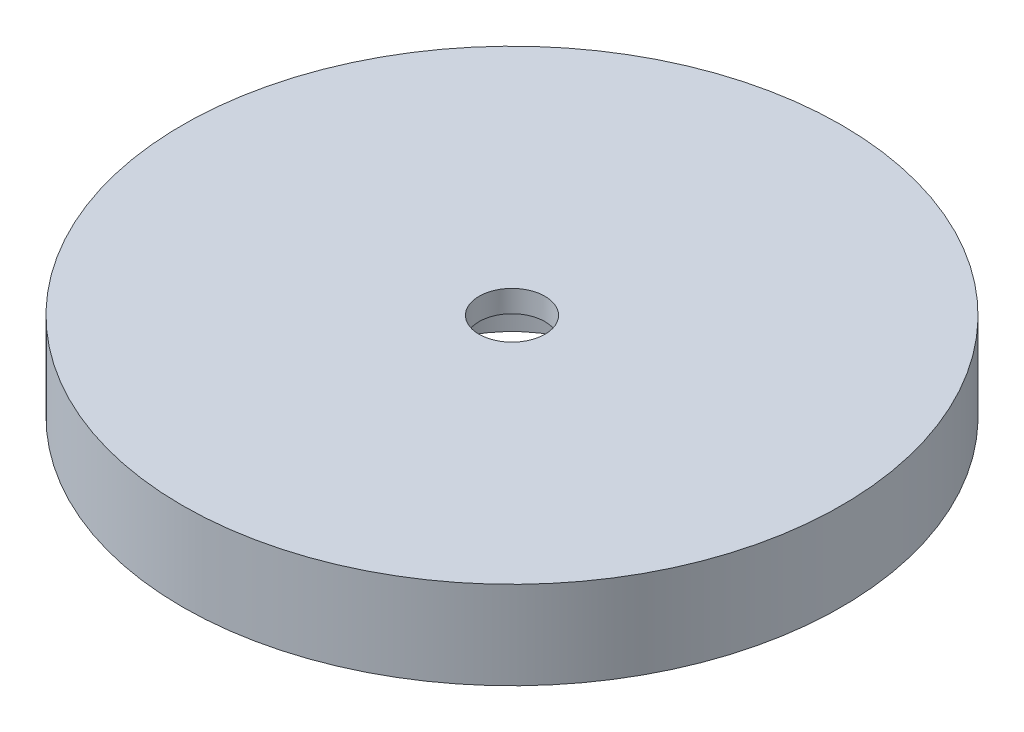
SolidWorks part; units mm, degrees
ref_plane "Plan de face" through (0, 0, 0) normal (0, 0, 1) x (1, 0, 0)
ref_plane "Plan de dessus" through (0, 0, 0) normal (0, 1, 0) x (1, 0, 0)
ref_plane "Plan de droite" through (0, 0, 0) normal (1, 0, 0) x (0, 0, -1)
sketch "Esquisse1" plane through (0, 0, 0) normal (0, 1, 0) x (1, 0, 0)
  circle A0 centre (0, 0) radius 30
  dimension "D1" = 60
extrude "Boss.-Extru.1" add sketch "Esquisse1" along normal blind 8
sketch "Esquisse2" plane through (0, 0, 0) normal (0, -1, 0) x (1, 0, 0)
  circle A0 centre (0, 0) radius 9.5
  dimension "D1" = 19
extrude "Enlèv. mat.-Extru.1" cut sketch "Esquisse2" against normal blind 6
sketch "Esquisse3" plane through (0, 8, 0) normal (0, 1, 0) x (1, 0, 0)
  circle A0 centre (0, 0) radius 3
  dimension "D1" = 6
extrude "Enlèv. mat.-Extru.2" cut sketch "Esquisse3" against normal through all
